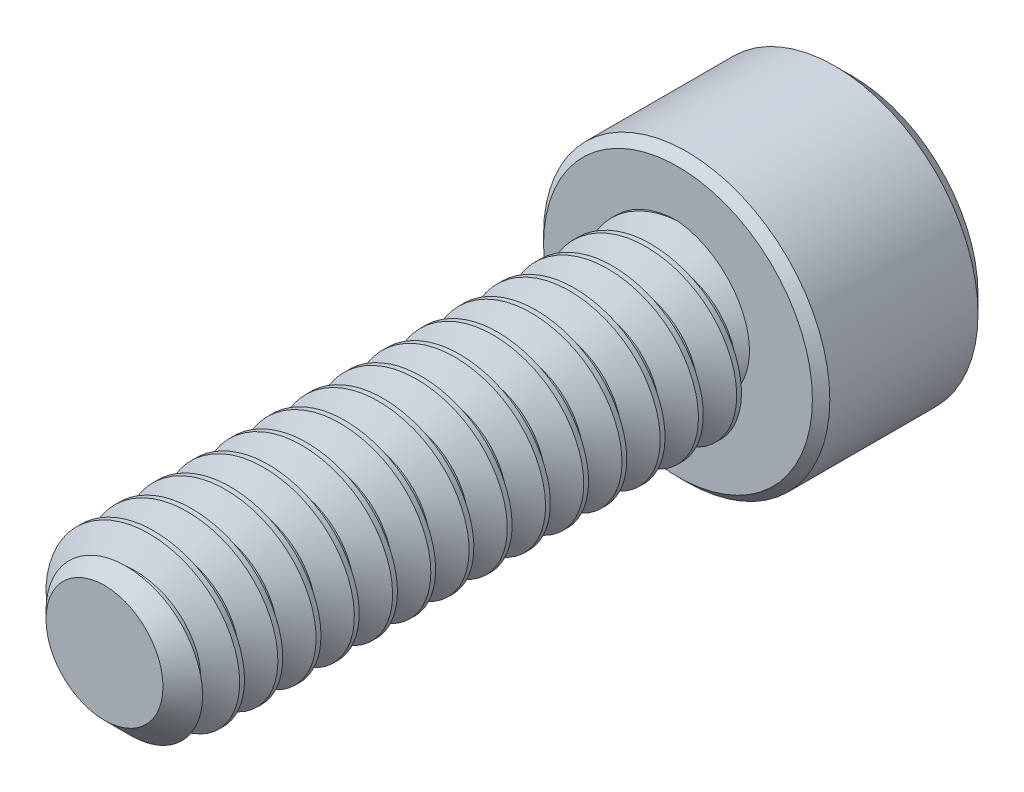
SolidWorks part; units mm, degrees
material "Alloy Steel"
ref_plane "Front Plane" through (0, 0, 0) normal (0, 0, 1) x (1, 0, 0)
ref_plane "Top Plane" through (0, 0, 0) normal (0, 1, 0) x (1, 0, 0)
ref_plane "Right Plane" through (0, 0, 0) normal (1, 0, 0) x (0, 0, -1)
sketch "Sketch1" plane through (0, 0, 0) normal (0, 0, 1) x (1, 0, 0)
  line L0 (0, 2.413) -> (0, -2.413) construction
  circle A0 centre (0, 0) radius 2.413
  dimension "OD" = 4.826
extrude "Extrude1" add sketch "Sketch1" against normal blind 15.875
sketch "Sketch2" plane through (0, 0, 0) normal (0, 0, 1) x (1, 0, 0)
  circle A0 centre (0, 0) radius 2.413 construction
  circle A1 centre (0, 0) radius 2.413
curve "Helix/Spiral1" pitch 1.0583 height 16.9333 turns 16 parameters "pitch"=1.0583
chamfer "Chamfer3" distance 0.7937 angle 45 1 edges at (2.413, 0, 0)
sketch "Sketch3" plane through (0, 0, 0) normal (1, 0, 0) x (0, 0, -1)
  line L0 (-0.926, 2.413) -> (-0.5292, 1.7256)
  line L1 (-0.5292, 1.7256) -> (-0.3969, 1.7256)
  line L2 (-0.3969, 1.7256) -> (0, 2.413)
  line L3 (-0.926, 2.413) -> (0, 2.413)
  line L4 (-0.463, 2.413) -> (-0.463, 1.7256) construction
  line L5 (-0.7276, 2.0693) -> (-0.1984, 2.0693) construction
  line L6 (0, 2.413) -> (0, -2.413) construction
  dimension "D1" = 0.1323
  dimension "D2" = 0.5292
  dimension "D3" = 60
sweep "Cut-Sweep1" cut profiles "Sketch3" path "Helix/Spiral1"
sketch "Sketch6" plane through (0, 0, -15.875) normal (0, 0, -1) x (-1, 0, 0)
  circle A0 centre (0, 0) radius 3.9624
  dimension "head dia" = 7.9248
extrude "Extrude2" add sketch "Sketch6" along normal blind 4.826
sketch "Sketch7" plane through (0, 0, -20.701) normal (0, 0, -1) x (-1, 0, 0)
  line L1 (0, 2.2914) -> (-1.9844, 1.1457)
  line L2 (-1.9844, 1.1457) -> (-1.9844, -1.1457)
  line L3 (-1.9844, -1.1457) -> (0, -2.2914)
  line L4 (0, -2.2914) -> (1.9844, -1.1457)
  line L5 (1.9844, -1.1457) -> (1.9844, 1.1457)
  line L6 (1.9844, 1.1457) -> (0, 2.2914)
  circle A0 centre (0, 0) radius 1.9844 construction
  dimension "hex dia" = 3.9688
extrude "Cut-Extrude1" cut sketch "Sketch7" against normal blind 2.9766
sketch "Sketch8" plane through (0, 0, -20.701) normal (0, 0, -1) x (-1, 0, 0)
  circle A0 centre (0, 0) radius 2.2914
extrude "Cut-Extrude2" cut sketch "Sketch8" against normal blind 0.4826 draft 45
chamfer "Chamfer1" distance 0.4826 angle 45 1 edges at (-3.9624, 0, -20.701)
chamfer "Chamfer2" distance 0.2413 angle 45 1 edges at (-3.9624, 0, -15.875)
sketch "Sketch9" plane through (0, 0, 0) normal (1, 0, 0) x (0, 0, -1)
  line L0 (0, 2.413) -> (0, -2.413) construction
  line L1 (5.8208, 2.413) -> (5.8208, -2.413) construction
  line L2 (15.875, 3.9624) -> (15.875, -3.9624) construction
  line L3 (20.701, 3.9624) -> (20.701, -3.9624) construction
  line L4 (20.701, 0) -> (0, 0) construction
  dimension "D1" = 5.8208
  dimension "D2" = 4.826
  dimension "D3" = 7.9248
  dimension "D4" = 15.875
equation "\"D3@Helix/Spiral1\" = \"screw length@Extrude1\"+\"pitch@Helix/Spiral1\""
equation "\"D1@Sketch3\" = \"pitch@Helix/Spiral1\"*.125"
equation "\"D2@Sketch3\" = \"pitch@Helix/Spiral1\"*.5"
equation "\"D1@Cut-Extrude1\" = \"hex dia@Sketch7\"*.75"
equation "\"D1@Chamfer1\" = \"head depth@Extrude2\"/10"
equation "\"D1@Sketch9\" = \"pitch@Helix/Spiral1\"*5.5"
equation "\"D1@Chamfer2\" = \"D1@Chamfer1\"/2"
equation "\"D1@Cut-Extrude2\" = \"D1@Chamfer2\"*2"
equation "\"D1@Chamfer3\" = \"pitch@Helix/Spiral1\"*.750"
equation "\"D2@Sketch9\" = \"head depth@Extrude2\""
equation "\"D3@Sketch9\" = \"head dia@Sketch6\""
equation "\"D4@Sketch9\" = \"screw length@Extrude1\""
